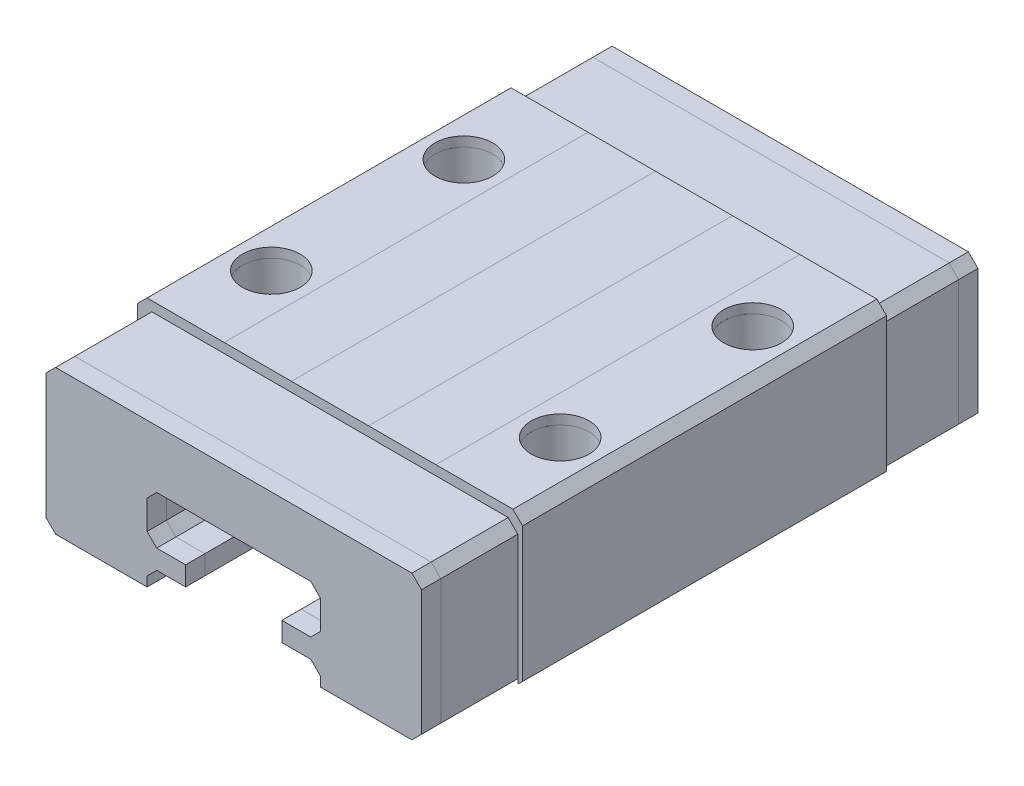
SolidWorks part; units mm, degrees
ref_plane "前视基准面" through (0, 0, 0) normal (0, 0, 1) x (1, 0, 0)
ref_plane "上视基准面" through (0, 0, 0) normal (0, 1, 0) x (1, 0, 0)
ref_plane "右视基准面" through (0, 0, 0) normal (1, 0, 0) x (0, 0, -1)
sketch "草图1" plane through (0, 0, 0) normal (0, 0, 1) x (1, 0, 0)
  line L0 (0, 0) -> (9, 0) construction
  line L1 (9, 2) -> (9, 3)
  line L2 (9, 3) -> (7, 3)
  line L3 (7, 3) -> (7, 4)
  line L4 (7, 4) -> (9, 4)
  line L5 (9, 4) -> (9, 6.5)
  line L6 (9, 6.5) -> (0, 6.5)
  line L7 (4.5, 6.5) -> (4.5, 0) construction
  line L8 (9, 4) -> (9, 3) construction
  line L9 (0, 2) -> (0, 3)
  line L10 (0, 3) -> (2, 3)
  line L11 (2, 3) -> (2, 4)
  line L12 (2, 4) -> (0, 4)
  line L13 (0, 4) -> (0, 6.5)
  line L14 (0, 2) -> (-5.25, 2)
  line L15 (-5.25, 2) -> (-5.25, 9.5)
  line L16 (-5.25, 9.5) -> (14.25, 9.5)
  line L17 (14.25, 9.5) -> (14.25, 2)
  line L18 (14.25, 2) -> (9, 2)
  line L19 (4.5, 9.5) -> (4.5, 6.5) construction
  line L20 (0, 2) -> (9, 2) construction
  line L21 (0, 2) -> (0, 0) construction
  line L22 (9, 2) -> (9, 0) construction
  dimension "D1" = 9
  dimension "D2" = 2
  dimension "D3" = 6.5
  dimension "D4" = 3.5
  dimension "D5" = 1
  dimension "D6" = 9.5
  dimension "D7" = 2
  dimension "D8" = 19.5
extrude "凸台-拉伸1" add sketch "草图1" along normal mid plane 28.9
chamfer "倒角2" distance 0.5 angle 45 10 edges at (9, 6.5, 0) (0, 6.5, 0) (9, 3, 0) (9, 4, 0) (0, 3, 0) (0, 4, 0) (14.25, 9.5, 0) (-5.25, 9.5, 0) (14.25, 2, 0) (-5.25, 2, 0)
sketch "草图2" plane through (0, 0, 0) normal (0, 0, 1) x (1, 0, 0)
  line L0 (-5.25, 2) -> (-5.25, 9.5)
  line L1 (-5.25, 9.5) -> (14.25, 9.5)
  line L2 (14.25, 9.5) -> (14.25, 2)
  line L3 (14.25, 2) -> (14.5, 2)
  line L4 (14.5, 2) -> (14.5, 10)
  line L5 (14.5, 10) -> (-5.5, 10)
  line L6 (-5.5, 10) -> (-5.5, 2)
  line L7 (-5.5, 2) -> (-5.25, 2)
  line L8 (4.5, 10) -> (4.5, 9.5) construction
  line L9 (-5.25, 2) -> (-4.75, 2) construction
  line L10 (13.75, 2) -> (14.25, 2) construction
  dimension "D1" = 8
  dimension "D2" = 20
extrude "凸台-拉伸2" add sketch "草图2" along normal mid plane 18.9 separate body
chamfer "倒角3" distance 0.5 angle 45 4 edges at (14.5, 2, 0) (-5.5, 2, 0) (14.5, 10, 0) (-5.5, 10, 0)
chamfer "倒角4" distance 0.5 angle 45 2 edges at (14.25, 9.5, 0) (-5.25, 9.5, 0)
sketch "草图3" plane through (0, 0, 0) normal (0, 1, 0) x (1, 0, 0)
  line L0 (-5.25, -13.45) -> (14.25, -13.45)
  line L1 (-5.25, -14.45) -> (-5.25, 14.45) construction
  line L2 (14.25, 14.45) -> (14.25, -14.45) construction
  line L3 (-5.25, 13.45) -> (14.25, 13.45)
  line L4 (13.75, -14.45) -> (-4.75, -14.45) construction
  line L5 (13.75, 14.45) -> (-4.75, 14.45) construction
  dimension "D1" = 1
  dimension "D2" = 1
sketch "草图4" plane through (0, 0, 0) normal (0, 1, 0) x (1, 0, 0)
  line L0 (-1, 9.45) -> (-1, -9.45)
  line L1 (14, 9.45) -> (-5, 9.45) construction
  line L2 (14, -9.45) -> (-5, -9.45) construction
  line L3 (2.5, 9.45) -> (2.5, -9.45)
  line L4 (6.5, 9.45) -> (6.5, -9.45)
  line L5 (10, 9.45) -> (10, -9.45)
  line L6 (-5, 9.45) -> (-5, -9.45) construction
  line L7 (14, -9.45) -> (14, 9.45) construction
  point P16 (14, 0)
  dimension "D1" = 4
  dimension "D2" = 4
  dimension "D3" = 3.5
  dimension "D4" = 3.5
split line "分割线1"
split line "分割线2"
sketch "草图5" plane through (0, 10, 0) normal (0, 1, 0) x (1, 0, 0)
  line L0 (-3, 5) -> (-3, -5) construction
  line L3 (-3, 0) -> (-5, 0) construction
  line L6 (-3, 5) -> (12, 5) construction
  line L7 (12, 5) -> (12, -5) construction
  line L8 (12, -5) -> (-3, -5) construction
  line L9 (4.5, 5) -> (4.5, 9.45) construction
  line L10 (6.5, 9.45) -> (2.5, 9.45) construction
  line L11 (-5, 9.45) -> (-5, -9.45) construction
  circle A0 centre (-3, 5) radius 1.5
  circle A1 centre (-3, -5) radius 1.5
  circle A2 centre (12, 5) radius 1.5
  circle A3 centre (12, -5) radius 1.5
  dimension "D1" = 3
  dimension "D2" = 3
  dimension "D4" = 3
  dimension "D5" = 3
  dimension "D3" = 10
  dimension "D6" = 15
extrude "切除-拉伸1" cut sketch "草图5" against normal blind 8
